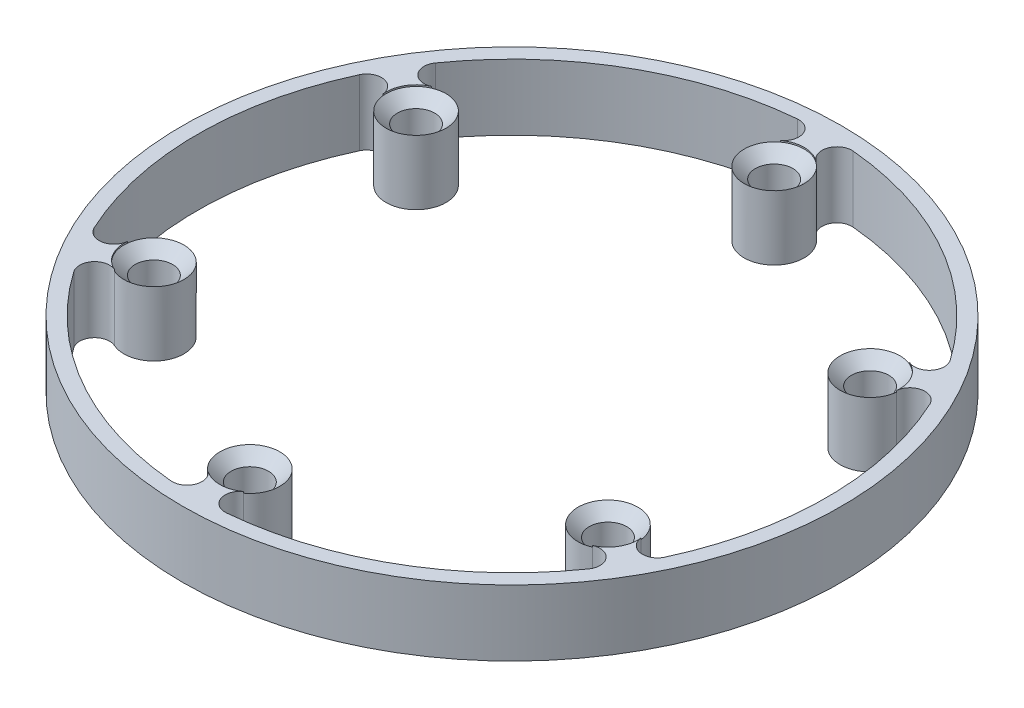
SolidWorks part; units mm, degrees
ref_plane "Front Plane" through (0, 0, 0) normal (0, 0, 1) x (1, 0, 0)
ref_plane "Top Plane" through (0, 0, 0) normal (0, 1, 0) x (1, 0, 0)
ref_plane "Right Plane" through (0, 0, 0) normal (1, 0, 0) x (0, 0, -1)
sketch "Sketch1" plane through (0, 0, 0) normal (0, 1, 0) x (1, 0, 0)
  circle A0 centre (0, 0) radius 22
  dimension "D1" = 44
extrude "Base shape" add sketch "Sketch1" along normal blind 4.4
sketch "Sketch4" plane through (0, 4.4, 0) normal (0, 1, 0) x (1, 0, 0)
  line L0 (0, 22) -> (0, -22) construction
  line L1 (-1, 17.5) -> (-2, 17.5) construction
  line L2 (-0.5, 15.5635) -> (0.5, 15.5635)
  line L3 (-0.5, 15.5635) -> (-0.5, 2.958)
  line L4 (-0.5, 2.958) -> (0.5, 2.958)
  line L5 (0.5, 15.5635) -> (0.5, 2.958)
  line L6 (-0.5, 15.5635) -> (0.5, 2.958) construction
  line L7 (-0.5, 2.958) -> (0.5, 15.5635) construction
  line L8 (-22, 0) -> (-21, 0) construction
  line L9 (-2, 0) -> (-3, 0) construction
  line L10 (13.7284, 7.3487) -> (2.8117, 1.046)
  line L11 (13.2284, 8.2148) -> (2.3117, 1.912)
  line L12 (13.2284, -8.2148) -> (2.3117, -1.912)
  line L13 (13.7284, -7.3487) -> (2.8117, -1.046)
  line L14 (-0.5, -15.5635) -> (-0.5, -2.958)
  line L15 (0.5, -15.5635) -> (0.5, -2.958)
  line L16 (-13.7284, -7.3487) -> (-2.8117, -1.046)
  line L17 (-13.2284, -8.2148) -> (-2.3117, -1.912)
  line L18 (-13.2284, 8.2148) -> (-2.3117, 1.912)
  line L19 (-13.7284, 7.3487) -> (-2.8117, 1.046)
  circle A0 centre (0, 0) radius 21
  circle A1 centre (0, 0) radius 22 construction
  circle A2 centre (0, 17.5) radius 1
  circle A3 centre (0, 17.5) radius 2
  circle A4 centre (0, 0) radius 3
  circle A5 centre (0, 0) radius 2
  circle A6 centre (-1.7711, 19.9214) radius 1
  circle A7 centre (1.7711, 19.9214) radius 1
  circle A8 centre (16.3669, 11.4945) radius 1
  circle A9 centre (18.138, 8.4269) radius 1
  circle A10 centre (15.1554, 8.75) radius 1
  circle A11 centre (15.1554, 8.75) radius 2
  circle A12 centre (18.138, -8.4269) radius 1
  circle A13 centre (16.3669, -11.4945) radius 1
  circle A14 centre (15.1554, -8.75) radius 1
  circle A15 centre (15.1554, -8.75) radius 2
  circle A16 centre (1.7711, -19.9214) radius 1
  circle A17 centre (-1.7711, -19.9214) radius 1
  circle A18 centre (0, -17.5) radius 1
  circle A19 centre (0, -17.5) radius 2
  circle A20 centre (-16.3669, -11.4945) radius 1
  circle A21 centre (-18.138, -8.4269) radius 1
  circle A22 centre (-15.1554, -8.75) radius 1
  circle A23 centre (-15.1554, -8.75) radius 2
  circle A24 centre (-18.138, 8.4269) radius 1
  circle A25 centre (-16.3669, 11.4945) radius 1
  circle A26 centre (-15.1554, 8.75) radius 1
  circle A27 centre (-15.1554, 8.75) radius 2
  point P12 (0, 9.2608)
  point P74 (0, 0)
  point P84 (0, 18.5)
  dimension "D1" = 1
  dimension "D2" = 2
  dimension "D4" = 2
  dimension "D5" = 4
  dimension "D3" = 3.5
  dimension "D6" = 6
extrude "Spokes cut" cut sketch "Sketch4" against normal up to next contours A23 L16 A4 L3 A3 A6 A0 A21 | A11 A8 A0 A7 A3 L5 A4 L11 | A15 A12 A0 A9 A11 L10 A4 L13 | A19 A16 A0 A13 A15 L12 A4 L15 | A23 A20 A0 A17 A19 L14 A4 L17 | A6 | A7 | A2 | A10 | A8 | A9 | A12 | A13 | A14 | A16 | A17 | A18 | A20 | A21 | A22 | A5 | A27 A24 A0 A21 A23 L16 A4 L19 | A26 | A24 | A25 region at (-6.811, 4.4, -11.797) region at (6.811, 4.4, -11.797) region at (-1.7711, 4.4, -19.9214) region at (1.7711, 4.4, -19.9214) region at (-13.622, 4.4, 0) region at (-16.3669, 4.4, -11.4945) region at (13.622, 4.4, 0) region at (16.3669, 4.4, -11.4945) region at (-18.138, 4.4, -8.4269) region at (-6.811, 4.4, 11.797) region at (18.138, 4.4, -8.4269) region at (-18.138, 4.4, 8.4269) region at (-16.3669, 4.4, 11.4945) region at (6.811, 4.4, 11.797) region at (18.138, 4.4, 8.4269) region at (-1.7711, 4.4, 19.9214) region at (16.3669, 4.4, 11.4945) region at (1.7711, 4.4, 19.9214) region at (0, 4.4, -17.5) region at (0, 4.4, 0) region at (15.1554, 4.4, -8.75) region at (15.1554, 4.4, 8.75) region at (0, 4.4, 17.5) region at (-15.1554, 4.4, 8.75) region at (-15.1554, 4.4, -8.75)
fillet "Spoke fillets" radius 1 23 edges at (13.2284, 2.2, 8.2148) (0.5, 2.2, 2.958) (13.7284, 2.2, -7.3487) (-0.5, 2.2, -2.958) (13.2284, 2.2, -8.2148) (0.5, 2.2, -2.958) (2.8117, 2.2, 1.046) (0.5, 2.2, -15.5635) (-13.2284, 2.2, 8.2148) (0.5, 2.2, 15.5635) (2.3117, 2.2, 1.912) (-0.5, 2.2, 2.958) (-0.5, 2.2, -15.5635) (-0.5, 2.2, 15.5635) (13.7284, 2.2, 7.3487) (2.3117, 2.2, -1.912) (-2.8117, 2.2, 1.046) (-13.7284, 2.2, 7.3487) (-2.3117, 2.2, -1.912) (-13.2284, 2.2, -8.2148) (-13.7284, 2.2, -7.3487) (-2.8117, 2.2, -1.046) (2.8117, 2.2, -1.046)
sketch "Sketch3" [suppressed] plane through (0, 0, 0) normal (0, -1, 0) x (1, 0, 0)
  line L0 (-3.4641, 2) -> (3.4641, -2) construction
  line L1 (-2.9641, 2.866) -> (3.9641, -1.134)
  line L2 (-3.9641, 1.134) -> (2.9641, -2.866)
  line L3 (-8.1331, 5.273) -> (-8.6331, 4.407) construction
  line L4 (-2.3117, 1.912) -> (-13.9545, 8.634) construction
  line L5 (-3.4613, 1.421) -> (-14.4545, 7.7679) construction
  arc A0 (-2.9641, 2.866) -> (-3.9641, 1.134) centre (-3.4641, 2) ccw
  arc A1 (2.9641, -2.866) -> (3.9641, -1.134) centre (3.4641, -2) ccw
  point P2 (0, 0)
  point P14 (-4.3301, 2.5)
  point P15 (4.3301, -2.5)
  dimension "D1" = 2
  dimension "D2" = 10
extrude "Pin cut" [suppressed] cut sketch "Sketch3" against normal blind 2.5
sketch "Sketch5" [suppressed] plane through (0, 4.4, 0) normal (0, 1, 0) x (1, 0, 0)
  line L0 (0, 19) -> (0, 22) construction
  circle A0 centre (0, 0) radius 19
  circle A1 centre (0, 0) radius 22 construction
  circle A2 centre (0, 0) radius 22
  dimension "D1" = 3
extrude "Middle slot cut" [suppressed] cut sketch "Sketch5" against normal blind 1.3
sketch "Sketch6" plane through (0, 4.4, 0) normal (0, 1, 0) x (1, 0, 0)
  circle A0 centre (0, 17.5) radius 1.25
  circle A1 centre (15.1554, 8.75) radius 1.25
  circle A2 centre (15.1554, -8.75) radius 1.25
  circle A3 centre (0, -17.5) radius 1.25
  circle A4 centre (-15.1554, -8.75) radius 1.25
  circle A5 centre (-15.1554, 8.75) radius 1.25
  dimension "D1" = 2.5
extrude "Screw hole englargements" [suppressed] cut sketch "Sketch6" against normal up to next
sketch "Sketch9" [suppressed] plane through (0, 4.4, 0) normal (0, 1, 0) x (1, 0, 0)
  line L12 (13.1554, -7.0179) -> (3.4613, -1.421)
  line L13 (3.4613, 1.421) -> (13.1554, 7.0179)
  line L14 (12.6554, 7.884) -> (2.9613, 2.2871)
  line L15 (0.5, 3.7081) -> (0.5, 14.9019)
  line L16 (-0.5, 14.9019) -> (-0.5, 3.7081)
  line L17 (-2.9613, 2.2871) -> (-12.6554, 7.884)
  line L18 (-13.1554, 7.0179) -> (-3.4613, 1.421)
  line L19 (-3.4613, -1.421) -> (-13.1554, -7.0179)
  line L20 (-12.6554, -7.884) -> (-2.3117, -1.912)
  line L21 (-0.5, -3.7081) -> (-0.5, -14.9019)
  line L22 (0.5, -14.9019) -> (0.5, -3.7081)
  line L23 (2.9613, -2.2871) -> (12.6554, -7.884)
  line L24 (13.1554, -7.0179) -> (3.4613, -1.421)
  line L25 (3.4613, 1.421) -> (13.1554, 7.0179)
  line L26 (12.6554, 7.884) -> (2.9613, 2.2871)
  line L27 (0.5, 3.7081) -> (0.5, 14.9019)
  line L28 (-0.5, 14.9019) -> (-0.5, 3.7081)
  line L29 (-2.9613, 2.2871) -> (-12.6554, 7.884)
  line L30 (-13.1554, 7.0179) -> (-3.4613, 1.421)
  line L31 (-3.4613, -1.421) -> (-13.1554, -7.0179)
  line L32 (-12.6554, -7.884) -> (-2.3117, -1.912)
  line L33 (-0.5, -3.7081) -> (-0.5, -14.9019)
  line L34 (0.5, -14.9019) -> (0.5, -3.7081)
  line L35 (2.9613, -2.2871) -> (12.6554, -7.884)
  circle A0 centre (-15.1554, 8.75) radius 2
  arc A1 (-13.1554, 8.75) -> (-15.7224, 10.6679) centre (-15.1554, 8.75) ccw construction
  circle A2 centre (0, 17.5) radius 2
  arc A3 (1, 15.7679) -> (1.3775, 18.95) centre (0, 17.5) ccw construction
  circle A4 centre (15.1554, 8.75) radius 2
  arc A5 (14.1554, 7.0179) -> (17.0999, 8.2821) centre (15.1554, 8.75) ccw construction
  circle A6 centre (15.1554, -8.75) radius 2
  arc A7 (17.0999, -8.2821) -> (14.1554, -7.0179) centre (15.1554, -8.75) ccw construction
  circle A8 centre (0, -17.5) radius 2
  arc A9 (1.3775, -18.95) -> (1, -15.7679) centre (0, -17.5) ccw construction
  circle A10 centre (-15.1554, -8.75) radius 2
  arc A11 (-14.1554, -7.0179) -> (-17.0999, -8.2821) centre (-15.1554, -8.75) ccw construction
  arc A47 (-14.1554, 7.0179) -> (-13.1554, 8.75) centre (-15.1554, 8.75) ccw
  arc A48 (-14.1554, 7.0179) -> (-13.1554, 8.75) centre (-15.1554, 8.75) ccw
  arc A49 (-13.1554, -8.75) -> (-14.1554, -7.0179) centre (-15.1554, -8.75) ccw
  arc A50 (-13.1554, -8.75) -> (-14.1554, -7.0179) centre (-15.1554, -8.75) ccw
  arc A51 (1, -15.7679) -> (-1, -15.7679) centre (0, -17.5) ccw
  arc A52 (1, -15.7679) -> (-1, -15.7679) centre (0, -17.5) ccw
  arc A53 (14.1554, -7.0179) -> (13.1554, -8.75) centre (15.1554, -8.75) ccw
  arc A54 (14.1554, -7.0179) -> (13.1554, -8.75) centre (15.1554, -8.75) ccw
  arc A55 (13.1554, 8.75) -> (14.1554, 7.0179) centre (15.1554, 8.75) ccw
  arc A56 (13.1554, 8.75) -> (14.1554, 7.0179) centre (15.1554, 8.75) ccw
  arc A57 (-1, 15.7679) -> (1, 15.7679) centre (0, 17.5) ccw
  arc A58 (-1, 15.7679) -> (1, 15.7679) centre (0, 17.5) ccw
  arc A62 (13.1554, -7.0179) -> (14.1554, -7.0179) centre (13.6554, -6.1519) ccw
  arc A63 (2.971, -0.4163) -> (3.4613, -1.421) centre (3.9613, -0.555) ccw
  arc A64 (2.971, -0.4163) -> (2.971, 0.4163) centre (0, 0) ccw
  arc A65 (3.4613, 1.421) -> (2.971, 0.4163) centre (3.9613, 0.555) ccw
  arc A66 (14.1554, 7.0179) -> (13.1554, 7.0179) centre (13.6554, 6.1519) ccw
  arc A70 (12.6554, 7.884) -> (13.1554, 8.75) centre (12.1554, 8.75) ccw
  arc A71 (1.846, 2.3648) -> (2.9613, 2.2871) centre (2.4613, 3.1531) ccw
  arc A72 (1.846, 2.3648) -> (1.125, 2.7811) centre (0, 0) ccw
  arc A73 (0.5, 3.7081) -> (1.125, 2.7811) centre (1.5, 3.7081) ccw
  arc A74 (1, 15.7679) -> (0.5, 14.9019) centre (1.5, 14.9019) ccw
  arc A78 (-0.5, 14.9019) -> (-1, 15.7679) centre (-1.5, 14.9019) ccw
  arc A79 (-1.125, 2.7811) -> (-0.5, 3.7081) centre (-1.5, 3.7081) ccw
  arc A80 (-1.125, 2.7811) -> (-1.846, 2.3648) centre (0, 0) ccw
  arc A81 (-2.9613, 2.2871) -> (-1.846, 2.3648) centre (-2.4613, 3.1531) ccw
  arc A82 (-13.1554, 8.75) -> (-12.6554, 7.884) centre (-12.1554, 8.75) ccw
  arc A86 (-13.1554, 7.0179) -> (-14.1554, 7.0179) centre (-13.6554, 6.1519) ccw
  arc A87 (-2.971, 0.4163) -> (-3.4613, 1.421) centre (-3.9613, 0.555) ccw
  arc A88 (-2.971, 0.4163) -> (-2.971, -0.4163) centre (0, 0) ccw
  arc A89 (-3.4613, -1.421) -> (-2.971, -0.4163) centre (-3.9613, -0.555) ccw
  arc A90 (-14.1554, -7.0179) -> (-13.1554, -7.0179) centre (-13.6554, -6.1519) ccw
  arc A94 (-12.6554, -7.884) -> (-13.1554, -8.75) centre (-12.1554, -8.75) ccw
  arc A95 (-2.3117, -1.912) -> (-1.125, -2.7811) centre (0, 0) ccw
  arc A96 (-0.5, -3.7081) -> (-1.125, -2.7811) centre (-1.5, -3.7081) ccw
  arc A97 (-1, -15.7679) -> (-0.5, -14.9019) centre (-1.5, -14.9019) ccw
  arc A101 (0.5, -14.9019) -> (1, -15.7679) centre (1.5, -14.9019) ccw
  arc A102 (1.125, -2.7811) -> (0.5, -3.7081) centre (1.5, -3.7081) ccw
  arc A103 (1.125, -2.7811) -> (1.846, -2.3648) centre (0, 0) ccw
  arc A104 (2.9613, -2.2871) -> (1.846, -2.3648) centre (2.4613, -3.1531) ccw
  arc A105 (13.1554, -8.75) -> (12.6554, -7.884) centre (12.1554, -8.75) ccw
  arc A109 (13.1554, -7.0179) -> (14.1554, -7.0179) centre (13.6554, -6.1519) ccw
  arc A110 (2.971, -0.4163) -> (3.4613, -1.421) centre (3.9613, -0.555) ccw
  arc A111 (2.971, -0.4163) -> (2.971, 0.4163) centre (0, 0) ccw
  arc A112 (3.4613, 1.421) -> (2.971, 0.4163) centre (3.9613, 0.555) ccw
  arc A113 (14.1554, 7.0179) -> (13.1554, 7.0179) centre (13.6554, 6.1519) ccw
  arc A117 (12.6554, 7.884) -> (13.1554, 8.75) centre (12.1554, 8.75) ccw
  arc A118 (1.846, 2.3648) -> (2.9613, 2.2871) centre (2.4613, 3.1531) ccw
  arc A119 (1.846, 2.3648) -> (1.125, 2.7811) centre (0, 0) ccw
  arc A120 (0.5, 3.7081) -> (1.125, 2.7811) centre (1.5, 3.7081) ccw
  arc A121 (1, 15.7679) -> (0.5, 14.9019) centre (1.5, 14.9019) ccw
  arc A125 (-0.5, 14.9019) -> (-1, 15.7679) centre (-1.5, 14.9019) ccw
  arc A126 (-1.125, 2.7811) -> (-0.5, 3.7081) centre (-1.5, 3.7081) ccw
  arc A127 (-1.125, 2.7811) -> (-1.846, 2.3648) centre (0, 0) ccw
  arc A128 (-2.9613, 2.2871) -> (-1.846, 2.3648) centre (-2.4613, 3.1531) ccw
  arc A129 (-13.1554, 8.75) -> (-12.6554, 7.884) centre (-12.1554, 8.75) ccw
  arc A133 (-13.1554, 7.0179) -> (-14.1554, 7.0179) centre (-13.6554, 6.1519) ccw
  arc A134 (-2.971, 0.4163) -> (-3.4613, 1.421) centre (-3.9613, 0.555) ccw
  arc A135 (-2.971, 0.4163) -> (-2.971, -0.4163) centre (0, 0) ccw
  arc A136 (-3.4613, -1.421) -> (-2.971, -0.4163) centre (-3.9613, -0.555) ccw
  arc A137 (-14.1554, -7.0179) -> (-13.1554, -7.0179) centre (-13.6554, -6.1519) ccw
  arc A141 (-12.6554, -7.884) -> (-13.1554, -8.75) centre (-12.1554, -8.75) ccw
  arc A142 (-2.3117, -1.912) -> (-1.125, -2.7811) centre (0, 0) ccw
  arc A143 (-0.5, -3.7081) -> (-1.125, -2.7811) centre (-1.5, -3.7081) ccw
  arc A144 (-1, -15.7679) -> (-0.5, -14.9019) centre (-1.5, -14.9019) ccw
  arc A148 (0.5, -14.9019) -> (1, -15.7679) centre (1.5, -14.9019) ccw
  arc A149 (1.125, -2.7811) -> (0.5, -3.7081) centre (1.5, -3.7081) ccw
  arc A150 (1.125, -2.7811) -> (1.846, -2.3648) centre (0, 0) ccw
  arc A151 (2.9613, -2.2871) -> (1.846, -2.3648) centre (2.4613, -3.1531) ccw
  arc A152 (13.1554, -8.75) -> (12.6554, -7.884) centre (12.1554, -8.75) ccw
  dimension "D1" = 0
extrude "Remove inner" [suppressed] cut sketch "Sketch9" against normal up to next contours A152 A6 A109 L24 A110 A111 A112 L25 A113 A4 A117 L26 A118 A119 A120 L27 A121 A2 A125 L28 A126 A127 A128 L29 A129 A0 A133 L30 A134 A135 A136 L31 A137 A10 A141 L32 A142 A143 L33 A144 A8 A148 L34 A149 A150 A151 L35
sketch "Sketch10" plane through (0, 4.4, 0) normal (0, 1, 0) x (1, 0, 0)
  circle A0 centre (-15.1554, 8.75) radius 2
  circle A1 centre (0, 17.5) radius 2
  circle A2 centre (15.1554, 8.75) radius 2
  circle A3 centre (15.1554, -8.75) radius 2
  circle A4 centre (0, -17.5) radius 2
  circle A5 centre (-15.1554, -8.75) radius 2
  arc A6 (-17.1438, 8.5346) -> (-14.1554, 7.0179) centre (-15.1554, 8.75) ccw construction
  arc A7 (-1.1807, 19.1143) -> (-1, 15.7679) centre (0, 17.5) ccw construction
  arc A8 (15.9631, 10.5797) -> (13.1554, 8.75) centre (15.1554, 8.75) ccw construction
  arc A9 (17.1438, -8.5346) -> (14.1554, -7.0179) centre (15.1554, -8.75) ccw construction
  arc A10 (1.1807, -19.1143) -> (1, -15.7679) centre (0, -17.5) ccw construction
  arc A11 (-15.9631, -10.5797) -> (-13.1554, -8.75) centre (-15.1554, -8.75) ccw construction
  circle A12 centre (0, 0) radius 17.5
extrude "Remove inner 2" cut sketch "Sketch10" against normal up to next contours A4 A12 A3 A2 A1 A0 A5 region at (0, 4.4, 0)
hole_wizard "Outer M2 countersunks" positions "Sketch7" profile "Sketch8" countersink size "M2" standard "ANSI Metric" end condition through all
sketch "Sketch7" plane through (0, 4.4, 0) normal (0, 1, 0) x (1, 0, 0)
  point P0 (-15.1554, 8.75)
  point P3 (0, 17.5)
  point P6 (15.1554, 8.75)
  point P9 (15.1554, -8.75)
  point P12 (0, -17.5)
  point P15 (-15.1554, -8.75)
sketch "Sketch8" plane through (-15.1554, 4.4, -8.75) normal (1, 0, 0) x (0, 0, 1)
  line L0 (0, 0) -> (0, 4.4)
  line L1 (0, 4.4) -> (1.25, 4.4)
  line L2 (1.25, 4.4) -> (1.25, 0.85)
  line L3 (1.25, 0.85) -> (2, 0.1)
  line L4 (2, 0.1) -> (2, 0)
  line L6 (2, 0) -> (0, 0)
  line L7 (-1.25, 0.85) -> (-2, 0.1) construction
  line L11 (0, -6.35) -> (0, 107.95) construction
  dimension "Thru Hole Dia." = 2.5
  dimension "Thru Hole Depth" = 4.4
  dimension "C'Sink Dia." = 4
  dimension "C'Sink Angle" = 90
  dimension "Head Clearance" = 0.1
